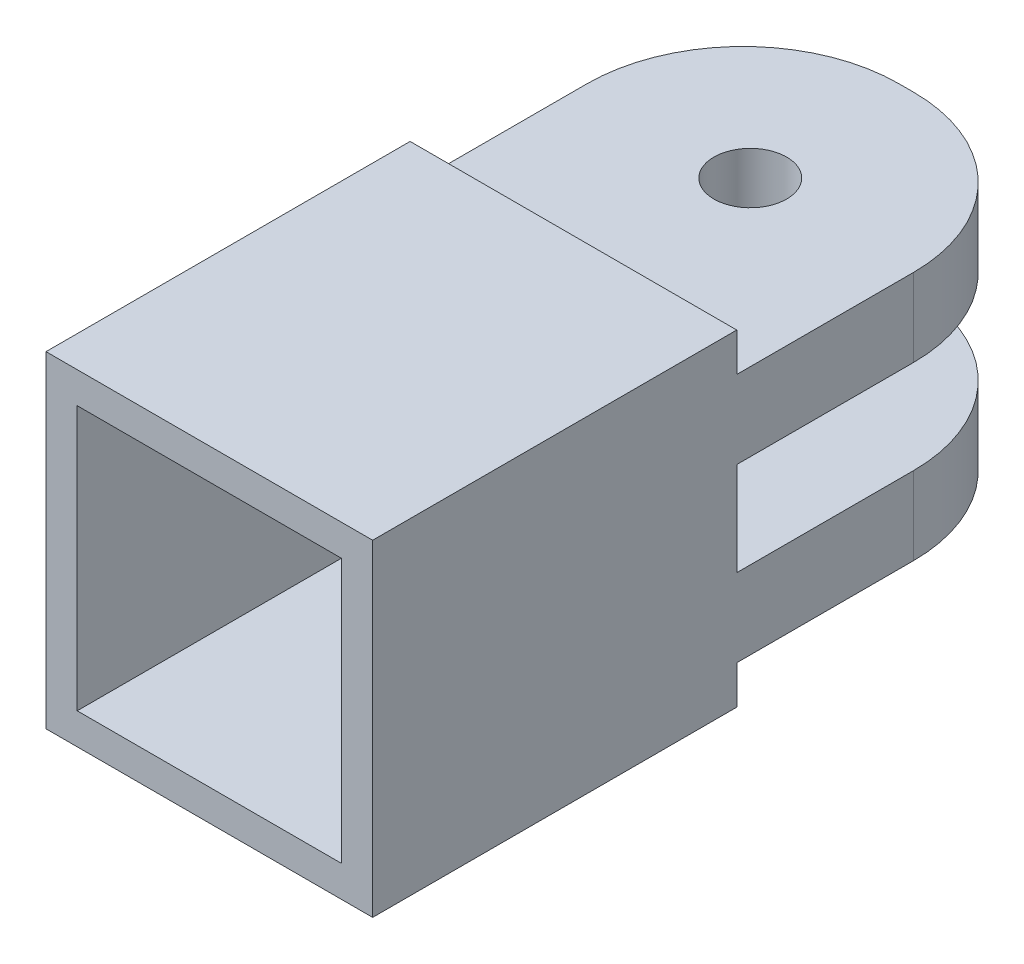
SolidWorks part; units mm, degrees
ref_plane "Front Plane" through (0, 0, 0) normal (0, 0, 1) x (1, 0, 0)
ref_plane "Top Plane" through (0, 0, 0) normal (0, 1, 0) x (1, 0, 0)
ref_plane "Right Plane" through (0, 0, 0) normal (1, 0, 0) x (0, 0, -1)
sketch "Sketch1" plane through (0, 0, 0) normal (0, 0, 1) x (1, 0, 0)
  line L0 (0, 34.2563) -> (0, -38.0151) construction
  line L1 (-50.9145, 0) -> (58.9447, 0) construction
  line L2 (-12.7, 12.7) -> (-12.7, -12.7)
  line L3 (-15.7, 15.7) -> (15.7, 15.7)
  line L4 (-15.7, 15.7) -> (-15.7, -15.7)
  line L5 (-15.7, -15.7) -> (15.7, -15.7)
  line L6 (15.7, 15.7) -> (15.7, -15.7)
  line L7 (-12.7, -12.7) -> (12.7, -12.7)
  line L8 (12.7, 12.7) -> (12.7, -12.7)
  line L9 (-12.7, 12.7) -> (12.7, 12.7)
  dimension "D1" = 15.7
  dimension "D2" = 15.7
  dimension "D3" = 15.7
  dimension "D4" = 15.7
  dimension "D5" = 3
extrude "Boss-Extrude1" add sketch "Sketch1" along normal blind 30
sketch "Sketch2" plane through (0, 0, 0) normal (0, 0, -1) x (-1, 0, 0)
  line L0 (15.7, 15.7) -> (15.7, -15.7)
  line L1 (15.7, -15.7) -> (-15.7, -15.7)
  line L2 (-15.7, -15.7) -> (-15.7, 15.7)
  line L3 (-15.7, 15.7) -> (15.7, 15.7)
extrude "Boss-Extrude2" add sketch "Sketch2" along normal blind 5
sketch "Sketch3" plane through (0, 0, -5) normal (0, 0, -1) x (-1, 0, 0)
  line L6 (-15.7, 12) -> (15.7, 12)
  line L7 (-15.7, 15.7) -> (-15.7, -15.7) construction
  line L8 (15.7, -15.7) -> (15.7, 15.7) construction
  line L9 (15.7, 12) -> (15.7, 4.5)
  line L10 (15.7, 4.5) -> (-15.7, 4.5)
  line L11 (-15.7, 4.5) -> (-15.7, 12)
  dimension "D1" = 7.5
  dimension "D2" = 4.5
extrude "Boss-Extrude3" add sketch "Sketch3" along normal blind 5
sketch "Sketch6" plane through (0, 12, 0) normal (0, 1, 0) x (1, 0, 0)
  line L0 (-15.7, 10) -> (-15.7, 22)
  line L1 (0.7, 37) -> (-0.7, 37)
  line L2 (15.7, 22) -> (15.7, 10)
  line L3 (15.7, 10) -> (-15.7, 10)
  arc A0 (-15.7, 22) -> (-0.7, 37) centre (-0.7, 22) cw
  arc A1 (0.7, 37) -> (15.7, 22) centre (0.7, 22) cw
  circle A2 centre (0, 22) radius 3.5
  point P10 (15.7, 37)
  dimension "D2" = 15
  dimension "D3" = 15
  dimension "D1" = 27
extrude "Boss-Extrude6" add sketch "Sketch6" against normal blind 7.5
mirror "Mirror1" about plane through (0, 0, 0) normal (0, 1, 0) of "Boss-Extrude6", "Boss-Extrude3"
